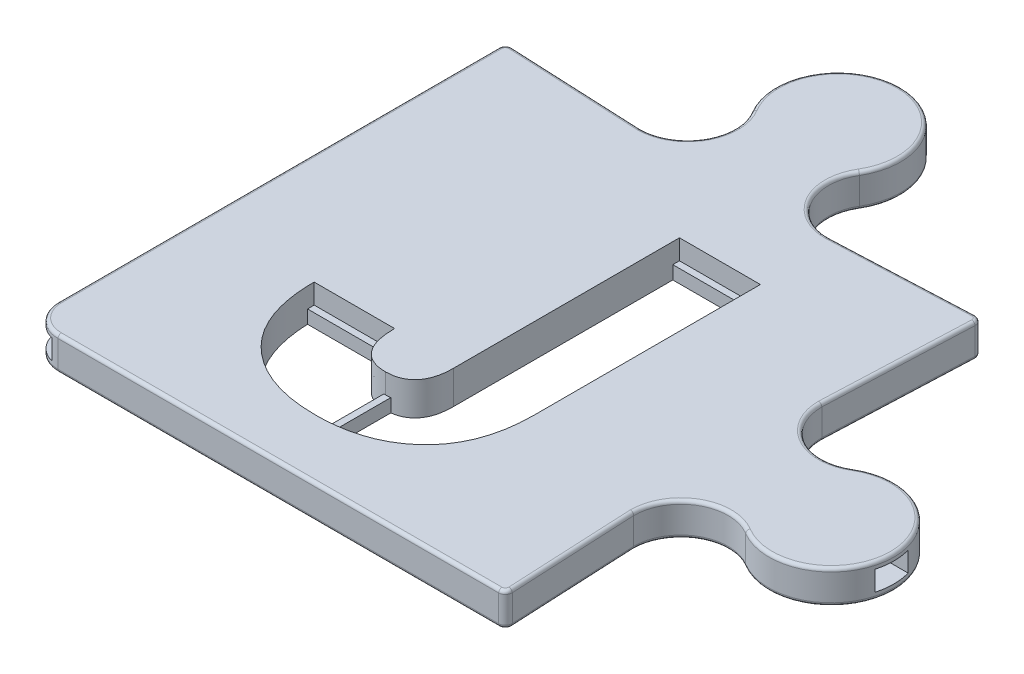
SolidWorks part; units mm, degrees
ref_plane "Front Plane" through (0, 0, 0) normal (0, 0, 1) x (1, 0, 0)
ref_plane "Top Plane" through (0, 0, 0) normal (0, 1, 0) x (1, 0, 0)
ref_plane "Right Plane" through (0, 0, 0) normal (1, 0, 0) x (0, 0, -1)
sketch "Sketch1" plane through (0, 0, 0) normal (0, 1, 0) x (1, 0, 0)
  line L0 (-31, -36) -> (37, -36) construction
  line L1 (-36, 37) -> (-36, -31) construction
  line L2 (-14.1421, 36) -> (-36, 37) construction
  line L3 (37, 37) -> (14.1421, 36) construction
  line L4 (36, 13.1421) -> (37, 37) construction
  line L5 (37, -36) -> (36, -15.1421) construction
  line L6 (-35.4, 36.3719) -> (-35.4, -31)
  line L7 (-36, 36) -> (36, 36) construction
  line L8 (-36, 36) -> (-36, -36) construction
  line L9 (-36, -36) -> (36, -36) construction
  line L10 (36, 36) -> (36, -36) construction
  line L11 (-31, -35.4) -> (36.3705, -35.4)
  line L12 (36.3705, -35.4) -> (35.4, -15.1568)
  line L13 (35.4, 13.155) -> (36.3732, 36.372)
  line L14 (36.3732, 36.372) -> (14.1555, 35.4)
  line L15 (-14.1562, 35.4) -> (-35.4, 36.3719)
  line L16 (-30, -24) -> (30, -24) construction
  line L17 (-30, 29) -> (30, 29) construction
  line L18 (-30, 29) -> (-30, -31) construction
  line L19 (-30, -31) -> (30, -31) construction
  line L20 (30, 29) -> (30, -31) construction
  line L21 (-30, 24) -> (30, 24) construction
  line L22 (-30, 24) -> (-30, -26) construction
  line L23 (-30, -26) -> (30, -26) construction
  line L24 (30, 24) -> (30, -26) construction
  arc A0 (-36, -31) -> (-31, -36) centre (-31, -31) ccw construction
  arc A1 (-14.1421, 36) -> (-8.571, 45.8485) centre (-14.1421, 42.5) ccw construction
  arc A2 (8.571, 45.8485) -> (-8.571, 45.8485) centre (0, 51) ccw construction
  arc A3 (8.571, 45.8485) -> (14.1421, 36) centre (14.1421, 42.5) ccw construction
  arc A4 (36, 13.1421) -> (45.8485, 7.571) centre (42.5, 13.1421) ccw construction
  arc A5 (45.8485, -9.571) -> (45.8485, 7.571) centre (51, -1) ccw construction
  arc A6 (45.8485, -9.571) -> (36, -15.1421) centre (42.5, -15.1421) ccw construction
  arc A7 (-35.4, -31) -> (-31, -35.4) centre (-31, -31) ccw
  arc A8 (46.1576, -9.0567) -> (35.4, -15.1568) centre (42.5, -15.1421) ccw
  arc A9 (46.1576, -9.0567) -> (46.1576, 7.0567) centre (51, -1) ccw
  arc A10 (35.4, 13.155) -> (46.1576, 7.0567) centre (42.5, 13.1421) ccw
  arc A11 (8.0567, 46.1576) -> (14.1555, 35.4) centre (14.1421, 42.5) ccw
  arc A12 (8.0567, 46.1576) -> (-8.0567, 46.1576) centre (0, 51) ccw
  arc A13 (-14.1562, 35.4) -> (-8.0567, 46.1576) centre (-14.1421, 42.5) ccw
  point P32 (36, 0)
  point P34 (0, 36)
  dimension "D5" = 6.5
  dimension "D6" = 10
  dimension "D7" = 6.5
  dimension "D13" = 5
  dimension "D9" = 10
  dimension "D11" = 6.5
  dimension "D12" = 6.5
  dimension "D1" = 72
  dimension "D2" = 1
  dimension "D3" = 1
  dimension "D4" = 15
  dimension "D8" = 1
  dimension "D10" = 35
  dimension "D14" = 15
  dimension "D15" = 36
  dimension "D16" = 1
  dimension "D18" = 60
  dimension "D19" = 60
  dimension "D20" = 5
  dimension "D21" = 6
  dimension "D22" = 5
  dimension "D23" = 50
  dimension "D24" = 2
  dimension "D17" = 0.6
extrude "Boss-Extrude1" add sketch "Sketch1" along normal blind 5
sketch "Sketch6" plane through (0, 0, 0) normal (0, -1, 0) x (1, 0, 0)
  line L0 (-35.4, -36.3719) -> (-35.4, 31) construction
  line L1 (-35.4, 17.9) -> (-27.4, 17.9)
  line L2 (-35.4, 17.9) -> (-35.4, -16.1)
  line L3 (-35.4, -16.1) -> (-27.4, -16.1)
  line L4 (-27.4, 17.9) -> (-27.4, -16.1)
  line L5 (-31, 35.4) -> (36.3705, 35.4) construction
  line L6 (-35.4, 14.65) -> (-30.4, 14.65)
  line L7 (-35.4, 14.65) -> (-35.4, -12.85)
  line L8 (-35.4, -12.85) -> (-30.4, -12.85)
  line L9 (-30.4, 14.65) -> (-30.4, -12.85)
  point P15 (-27.4, 0.9)
  point P16 (-30.4, 0.9)
  line M28 (-35.4, 31) -> (-35.4, -36.3719)
  dimension "D1" = 8
  dimension "D2" = 20.75
  dimension "D3" = 27.5
  dimension "D4" = 5
  dimension "D5" = 34
extrude "Cut-Extrude3" cut sketch "Sketch6" against normal blind 3 from offset 1 contours L6 L9 L8 L3 L4 L1 M28 | L9 L6 L2 L8 region at (-29.8665, 0, 0.9) region at (-32.9, 0, 0.9) offset against normal yes
extrude "Cut-Extrude4" cut sketch "Sketch6<3>" against normal up to next contours L9 L6 L2 L8 region at (-32.9, 0, 0.9)
sketch "Sketch6<3>" plane through (0, 0, 0) normal (0, -1, 0) x (1, 0, 0) same geometry as "Sketch6"
sketch "Sketch8" plane through (0, 0, 0) normal (0, -1, 0) x (1, 0, 0)
  line L1 (-2.5, -51.4) -> (2.5, -51.4)
  line L2 (-2.5, -51.4) -> (-2.5, -60.4)
  line L3 (-2.5, -60.4) -> (2.5, -60.4)
  line L4 (2.5, -51.4) -> (2.5, -60.4)
  line L5 (51.4, 3.5) -> (60.4, 3.5)
  line L6 (51.4, 3.5) -> (51.4, -1.5)
  line L7 (51.4, -1.5) -> (60.4, -1.5)
  line L8 (60.4, 3.5) -> (60.4, -1.5)
  arc A0 (-8.0567, -46.1576) -> (8.0567, -46.1576) centre (0, -51) ccw construction
  arc A1 (46.1576, -7.0567) -> (46.1576, 9.0567) centre (51, 1) ccw construction
  point P4 (0, -60.4)
  point P13 (60.4, 1)
  dimension "D1" = 5
  dimension "D2" = 9
  dimension "D3" = 5
  dimension "D4" = 9
extrude "Cut-Extrude5" cut sketch "Sketch8" against normal blind 3 from offset 1 offset against normal yes
sketch "Sketch9" plane through (0, 0, 0) normal (0, -1, 0) x (1, 0, 0)
  line L0 (-31, 35.4) -> (36.3705, 35.4) construction
  line L1 (-35.4, 14.65) -> (-35.4, 31) construction
  line L2 (-31.7636, 35.3332) -> (-35.4, 31) construction
  line L3 (-33.2571, 29.735) -> (-30.0429, 33.565) construction
  line L4 (-30.0429, 33.565) -> (-33.2571, 29.735) construction
  line L5 (-30.0429, 33.565) -> (-32.7119, 35.8048)
  line L6 (-33.2571, 29.735) -> (-35.926, 31.9747)
  line L7 (-32.7119, 35.8048) -> (-35.926, 31.9747)
  circle A0 centre (-31.65, 31.65) radius 2.5
  arc A1 (-31, 35.4) -> (-35.4, 31) centre (-31, 31) ccw construction
  arc M41 (-31, 35.4) -> (-35.4, 31) centre (-31, 31) ccw
  dimension "D1" = 5
  dimension "D3" = 3.75
  dimension "D4" = 5.6569
  dimension "D2" = 3.75
extrude "Cut-Extrude6" cut sketch "Sketch9" against normal blind 3 from offset 1 contours A0 L5 L6 M41 | A0 L5 region at (-33.6239, 0, 33.3064) region at (-31.65, 0, 31.65) offset against normal yes
sketch "Sketch11" plane through (-35.4, 0, 0) normal (-1, 0, 0) x (0, 0, 1)
  line L0 (-13.155, 0) -> (-36.372, 0) construction
  line L1 (-25.1, 3) -> (-19.1, 3)
  line L2 (-25.1, 3) -> (-25.1, 1.5)
  line L3 (-25.1, 1.5) -> (-19.1, 1.5)
  line L4 (-19.1, 3) -> (-19.1, 1.5)
  line L5 (-16.1, 4) -> (-16.1, 1) construction
  line L6 (35.4, 0) -> (15.1568, 0) construction
  line L7 (20.9, 3) -> (26.9, 3)
  line L8 (20.9, 3) -> (20.9, 1.5)
  line L9 (20.9, 1.5) -> (26.9, 1.5)
  line L10 (26.9, 3) -> (26.9, 1.5)
  line L12 (17.9, 4) -> (17.9, 1) construction
  dimension "D1" = 3
  dimension "D2" = 1.5
  dimension "D3" = 3
  dimension "D4" = 6
  dimension "D5" = 3
  dimension "D6" = 1.5
  dimension "D7" = 6
  dimension "D8" = 3
fillet "Fillet1" radius 0.5 17 edges at (-35.4, 0, 22.825) (-34.1113, 0, 34.1113) (2.6853, 0, 35.4) (35.8853, 0, 25.2784) (38.9978, 0, 8.966) (60.4, 0, 1) (38.9986, 0, -6.9655) (35.8866, 0, -24.7635) (25.2643, 0, -35.886) (7.9657, 0, -38.9984) (0, 0, -60.4) (-7.9658, 0, -38.9981) (-24.7781, 0, -35.886) (-35.4, 0, -24.611) (-32.9, 0, -12.85) (-30.4, 0, 0.9) (-32.9, 0, 14.65)
fillet "Fillet2" radius 0.5 13 edges at (-7.9658, 5, -38.9981) (0, 5, -60.4) (7.9657, 5, -38.9984) (25.2643, 5, -35.886) (35.8866, 5, -24.7635) (38.9986, 5, -6.9655) (60.4, 5, 1) (38.9978, 5, 8.966) (35.8853, 5, 25.2784) (2.6853, 5, 35.4) (-34.1113, 5, 34.1113) (-35.4, 5, -2.686) (-24.7781, 5, -35.886)
fillet "Fillet3" radius 1 9 edges at (36.2202, 0.1464, -36.2187) (36.2202, 4.8536, -36.2187) (36.3732, 2.5, -36.372) (-35.2536, 0.1464, -36.2186) (-35.2536, 4.8536, -36.2186) (36.2169, 0.1464, 35.2536) (36.2169, 4.8536, 35.2536) (36.3705, 2.5, 35.4) (-35.4, 2.5, -36.3719)
extrude "Cut-Extrude9" cut sketch "Sketch11" against normal blind 3
chamfer "Chamfer1" distance 1 angle 50 2 edges at (-35.4, 1.5, 23.9) (-35.4, 1.5, -22.1) first distance on face at (-35.4, 2.25, -22.1)
sketch "Sketch12" plane through (0, 5, 0) normal (0, 1, 0) x (1, 0, 0)
  text T0 "J" font "Poppins" height 50
extrude "Cut-Extrude10" cut sketch "Sketch12" against normal through all
sketch "Sketch13" plane through (0, 0, 0) normal (0, -1, 0) x (1, 0, 0)
  line L0 (3.1327, 10.0478) -> (3.1327, -24) construction
  line L1 (-6.4401, 10.2646) -> (-18.5903, 10.2646)
  line L2 (-6.4401, 10.2646) -> (-6.4401, 9.2646)
  line L3 (-6.4401, 9.2646) -> (-18.5903, 9.2646)
  line L4 (-18.5903, 10.2646) -> (-18.5903, 9.2646)
  line L5 (3.1327, -23) -> (15.3133, -23)
  line L6 (3.1327, -23) -> (3.1327, -24)
  line L7 (3.1327, -24) -> (15.3133, -24)
  line L8 (15.3133, -23) -> (15.3133, -24)
  line L10 (-1.7603, 27.2807) -> (-0.7603, 27.2807)
  line L11 (-1.7603, 27.2807) -> (-1.7603, 13.4409)
  line L12 (-1.7603, 13.4409) -> (-0.7603, 13.4409)
  line L13 (-0.7603, 27.2807) -> (-0.7603, 13.4409)
  spline S0 degree 3 poles (-6.4819, 9.2646) (-6.4672, 9.7569) (-6.4397, 10.6825) (-6.2072, 11.9809) (-5.8106, 13.0916) (-5.2486, 14.0148) (-4.5211, 14.7429) (-3.6302, 15.2381) (-2.6071, 15.5512) (-1.878, 15.5846) (-1.4942, 15.6022) knots 0 0 0 0 0.160918 0.302614 0.429515 0.544562 0.653407 0.762107 0.874781 1 1 1 1 construction
  dimension "D1" = 1
  dimension "D2" = 1
  dimension "D3" = 1
extrude "Boss-Extrude2" add sketch "Sketch13" against normal blind 2
